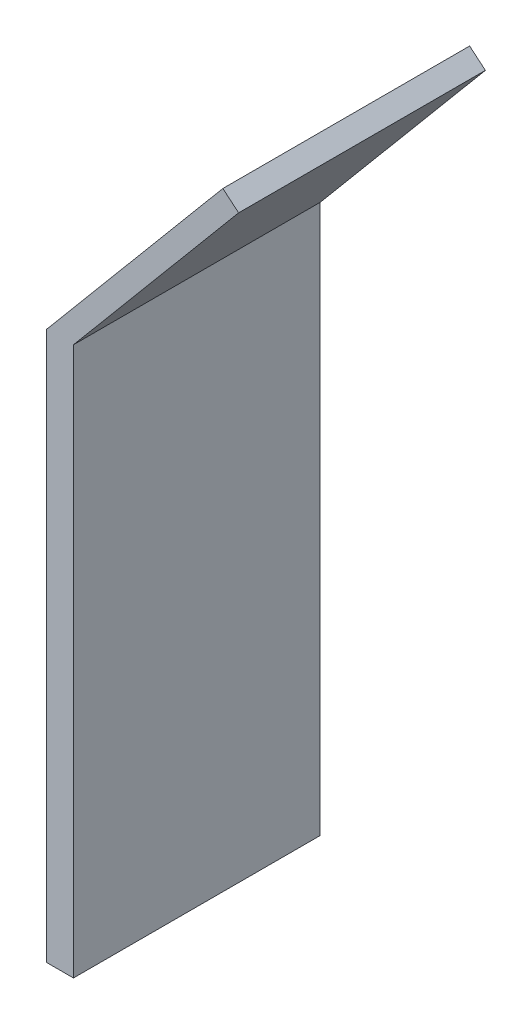
SolidWorks part; units mm, degrees
ref_plane "Plan de face" through (0, 0, 0) normal (0, 0, 1) x (1, 0, 0)
ref_plane "Plan de dessus" through (0, 0, 0) normal (0, 1, 0) x (1, 0, 0)
ref_plane "Plan de droite" through (0, 0, 0) normal (1, 0, 0) x (0, 0, -1)
sketch "Esquisse1" plane through (0, 0, 0) normal (0, 0, 1) x (1, 0, 0)
  line L0 (0, 0) -> (0, 80)
  line L1 (0, 80) -> (25.7115, 110.6418)
  line L2 (25.7115, 110.6418) -> (28.0096, 108.7134)
  line L3 (28.0096, 108.7134) -> (3.9162, 80)
  line L4 (3.9162, 80) -> (3.9162, 0)
  line L5 (3.9162, 0) -> (0, 0)
  line L6 (0, 80) -> (50000, 80) construction
  dimension "D1" = 80
  dimension "D2" = 40
  dimension "D3" = 3
  dimension "D4" = 50
extrude "Boss.-Extru.1" add sketch "Esquisse1" along normal blind 18 and the other way blind 18
